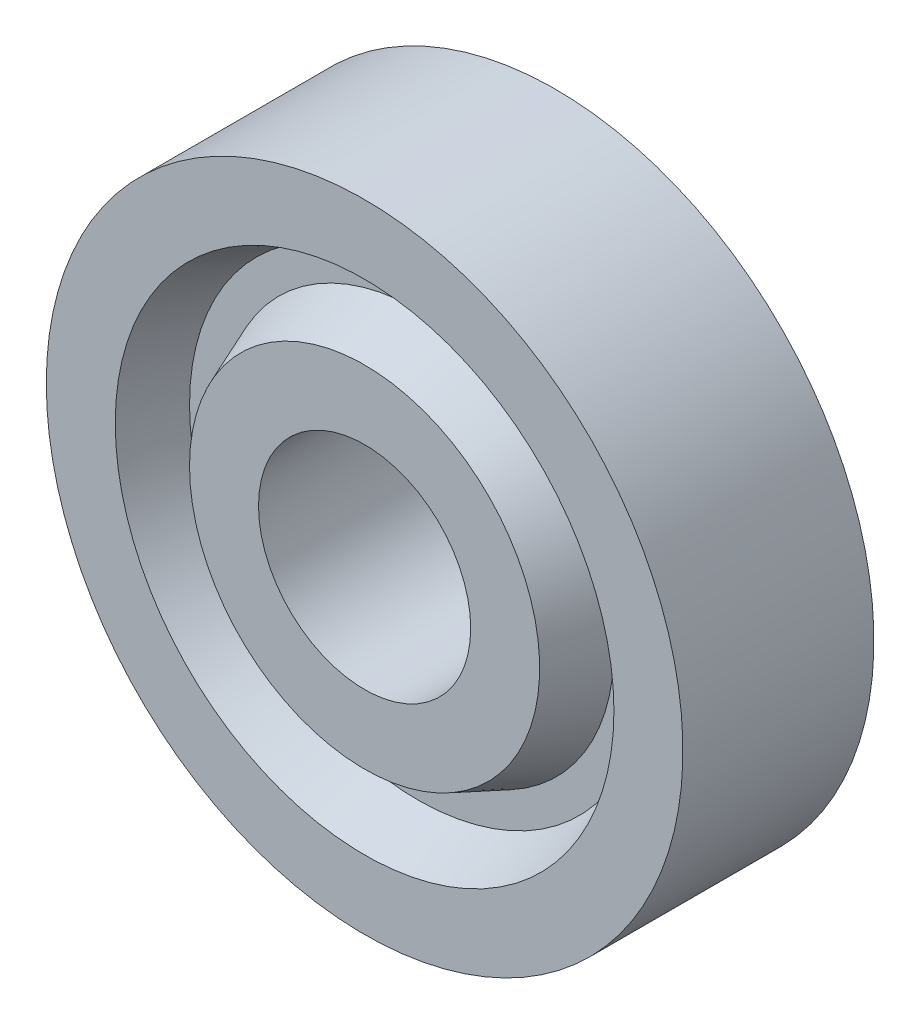
SolidWorks part; units mm, degrees
ref_plane "Front Plane" through (0, 0, 0) normal (0, 0, 1) x (1, 0, 0)
ref_plane "Top Plane" through (0, 0, 0) normal (0, 1, 0) x (1, 0, 0)
ref_plane "Right Plane" through (0, 0, 0) normal (1, 0, 0) x (0, 0, -1)
sketch "Sketch1" plane through (0, 0, 0) normal (0, 1, 0) x (1, 0, 0)
  line L0 (0, 28.9111) -> (0, -36.6207) construction
  line L2 (8.25, 4.5) -> (9.25, 2)
  line L3 (9.25, 2) -> (10.75, 2)
  line L4 (10.75, 2) -> (11.75, 4.5)
  line L6 (15, 4.5) -> (15, -4.5)
  line L8 (11.75, -4.5) -> (10.75, -2)
  line L9 (10.75, -2) -> (9.25, -2)
  line L10 (9.25, -2) -> (8.25, -4.5)
  line L12 (5, -4.5) -> (5, 4.5)
  line L13 (0, 0) -> (5, 0) construction
  line L14 (9.25, -2) -> (9.25, 2) construction
  line L15 (10.75, -2) -> (10.75, 2) construction
  line L16 (5, 4.5) -> (8.25, 4.5)
  line L17 (11.75, 4.5) -> (15, 4.5)
  line L18 (11.75, -4.5) -> (15, -4.5)
  line L19 (5, -4.5) -> (8.25, -4.5)
  line L20 (8.25, -4.5) -> (11.75, -4.5) construction
  line L21 (8.25, 4.5) -> (11.75, 4.5) construction
  line L22 (8.25, -4.5) -> (8.25, 4.5) construction
  line L23 (11.75, -4.5) -> (11.75, 4.5) construction
  dimension "D1" = 5
  dimension "D2" = 15
  dimension "D3" = 3.5
  dimension "D5" = 2.5
  dimension "D6" = 9
  dimension "D7" = 1.5
revolve "Revolve1" add sketch "Sketch1" angle 360 about L0
